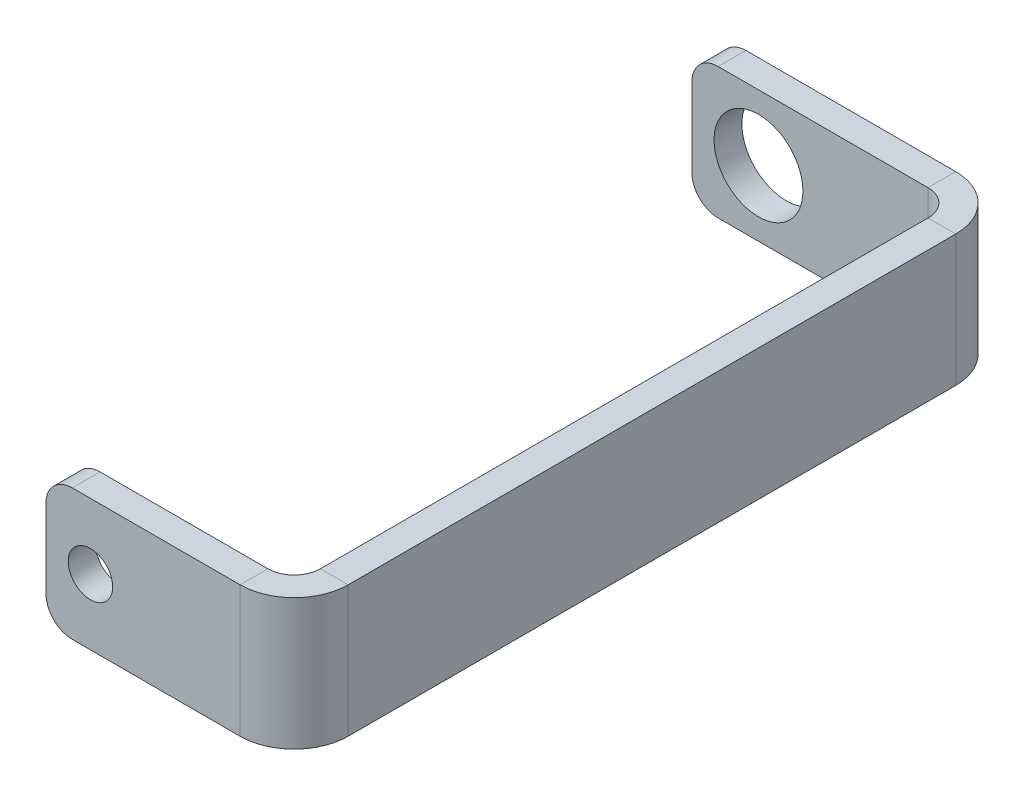
SolidWorks part; units mm, degrees
note: The reader was unsure of these and kept them because the rebuilt part matched: flange length of "Edge-Flange1", "Edge-Flange2".
material "Custom Plastic"
ref_plane "X-Y Datum" through (0, 0, 0) normal (0, 0, 1) x (1, 0, 0)
ref_plane "X-Z Datum" through (0, 0, 0) normal (0, 1, 0) x (1, 0, 0)
ref_plane "Y-Z Datum" through (0, 0, 0) normal (1, 0, 0) x (0, 0, -1)
sketch "Sketch1" plane through (0, 0, 0) normal (0, 0, 1) x (1, 0, 0)
  line L1 (-15, -7.5) -> (15, -7.5)
  line L2 (-15, -7.5) -> (-15, 7.5)
  line L3 (-15, 7.5) -> (15, 7.5)
  line L4 (15, -7.5) -> (15, 7.5)
  line L5 (-15, -7.5) -> (15, 7.5) construction
  line L6 (-15, 7.5) -> (15, -7.5) construction
  point P0 (0, 0)
  dimension "D1" = 30
  dimension "D2" = 15
base flange "Base-Flange1" sketch "Sketch1" thickness 3.175 reverse thickness direction no parameters "D1"=10
edge flange "Edge-Flange1" sketch "Sketch10" flange angle 90 flange length 78.652 flange position material outside bend radius 3 thickness 3.175 relief rectangular parameters "D6"=10
sketch "Sketch10" plane through (15, 0, 0) normal (-1, 0, 0) x (0, -1, 0)
  line L2 (-7.5, 0) -> (-7.5, 75.477)
  line L3 (-7.5, 75.477) -> (7.5, 75.477)
  line L4 (7.5, 75.477) -> (7.5, 0)
  line L5 (7.5, 0) -> (-7.5, 0) construction
  line L6 (7.5, 0) -> (-7.5, 0)
bend "EdgeBend1" bend radius 3 bend angle 90 parameters "D5"=1
edge flange "Edge-Flange2" sketch "Sketch13" flange angle 90 flange length 28.37 flange position material outside bend radius 3 thickness 3.175 relief rectangular parameters "D6"=10
sketch "Sketch13" plane through (15, 0, 75.477) normal (0, 0, -1) x (0, -1, 0)
  line L2 (-7.5, 0) -> (-7.5, 25.195)
  line L3 (-7.5, 25.195) -> (7.5, 25.195)
  line L4 (7.5, 25.195) -> (7.5, 0)
  line L5 (7.5, 0) -> (-7.5, 0) construction
  line L6 (7.5, 0) -> (-7.5, 0)
bend "EdgeBend2" bend radius 3 bend angle 90 parameters "D5"=2
sketch "Sketch14" plane through (0, 0, 0) normal (0, 0, 1) x (1, 0, 0)
  line L0 (-15, 0) -> (-7.38, 0)
  line L1 (-15, 7.5) -> (-15, -7.5) construction
  circle A0 centre (-7.38, 0) radius 5.08
  dimension "D1" = 10.16
  dimension "D2" = 7.62
extrude "Cut-Extrude1" cut sketch "Sketch14" against normal through all
sketch "Sketch15" plane through (0, 0, 78.652) normal (0, 0, 1) x (1, 0, 0)
  line L0 (-10.195, 0) -> (-5.115, 0)
  line L1 (-10.195, -7.5) -> (-10.195, 7.5) construction
  circle A0 centre (-5.115, 0) radius 2.54
  dimension "D1" = 5.08
extrude "Cut-Extrude2" cut sketch "Sketch15" against normal blind 10
fillet "Fillet1" radius 3 4 edges at (-10.195, 7.5, 77.0645) (-10.195, -7.5, 77.0645) (-15, 7.5, -1.5875) (-15, -7.5, -1.5875)
sketch "Bend-Lines1" [suppressed] plane through (0, 0, 0) normal (0, 1, 0) x (1, 0, 0)
sketch "Bounding-Box1" [suppressed] plane through (0, 0, 0) normal (0, 1, 0) x (1, 0, 0)
sheet metal parameters "Sheet-Metal1" thickness 3.175 parameters "D1"=10
flat pattern "Flat-Pattern1" [suppressed]
sketch "Bend-Lines2" plane through (0, 0, 0) normal (0, 1, 0) x (1, 0, 0)
sketch3d "Bounding-Box2" [suppressed]
  line L0 (-15, -7.5, 0) -> (15, -7.5, 0) construction
  line L1 (-15, 7.5, 0) -> (15, 7.5, 0) construction
  line L2 (-15, -7.5, 0) -> (-15, 7.5, 0) construction
  line L3 (15, -7.5, 0) -> (15, 7.5, 0) construction
sheet metal parameters "Sheet-Metal2" thickness 3.175 parameters "D1"=10
flat pattern "Flat-Pattern1"
sketch "Bend-Lines2" plane through (0, 0, 0) normal (0, 0, 1) x (1, 0, 0)
  line L0 (15.603, -7.5) -> (15.603, 7.5) construction
  line L1 (15.603, -7.5) -> (15.603, 7.5) construction
sketch3d "Bounding-Box2" [suppressed]
  line L0 (-15, -7.5, 0) -> (63.031, -7.5, 0) construction
  line L1 (-15, 7.5, 0) -> (63.031, 7.5, 0) construction
  line L2 (-15, -7.5, 0) -> (-15, 7.5, 0) construction
  line L3 (63.031, -7.5, 0) -> (63.031, 7.5, 0) construction
bend of the flat pattern "Flatten-<EdgeBend1>1"
sheet metal parameters "Sheet-Metal3" thickness 3.175 parameters "D1"=10
flat pattern "Flat-Pattern1" [suppressed]
sketch "Bend-Lines2" plane through (0, 0, 0) normal (0, 0, 1) x (1, 0, 0)
  line L0 (15.603, -7.5) -> (15.603, 7.5) construction
  line L1 (15.603, -7.5) -> (15.603, 7.5) construction
  line L2 (63.634, -7.5) -> (63.634, 7.5) construction
  line L3 (63.634, -7.5) -> (63.634, 7.5) construction
sketch3d "Bounding-Box2" [suppressed]
  line L0 (-15, -7.5, 0) -> (85.0621, -7.5, 0) construction
  line L1 (-15, 7.5, 0) -> (85.0621, 7.5, 0) construction
  line L2 (-15, -7.5, 0) -> (-15, 7.5, 0) construction
  line L3 (85.0621, -7.5, 0) -> (85.0621, 7.5, 0) construction
bend of the flat pattern "Flatten-<EdgeBend1>1"
bend of the flat pattern "Flatten-<EdgeBend2>1"
sheet metal parameters "Sheet-Metal4" thickness 3.175 parameters "D1"=10
flat pattern "Flat-Pattern1" [suppressed]
sketch "Bend-Lines2" plane through (0, 0, 0) normal (0, 0, 1) x (1, 0, 0)
  line L0 (13.103, -7.5) -> (13.103, 7.5) construction
  line L1 (13.103, -7.5) -> (13.103, 7.5) construction
  line L2 (88.086, -7.5) -> (88.086, 7.5) construction
  line L3 (88.086, -7.5) -> (88.086, 7.5) construction
sketch3d "Bounding-Box2" [suppressed]
  line L0 (-12.5, -7.5, 0) -> (115.5141, -7.5, 0) construction
  line L1 (-12.5, 7.5, 0) -> (115.5141, 7.5, 0) construction
  line L2 (-12.5, -7.5, 0) -> (-12.5, 7.5, 0) construction
  line L3 (115.5141, -7.5, 0) -> (115.5141, 7.5, 0) construction
bend of the flat pattern "Flatten-<EdgeBend1>1"
bend of the flat pattern "Flatten-<EdgeBend2>1"
sheet metal parameters "Sheet-Metal5" thickness 3.175 parameters "D1"=10
flat pattern "Flat-Pattern1"
sketch "Bend-Lines2" plane through (0, 0, 0) normal (0, 0, 1) x (1, 0, 0)
  line L0 (15.603, -7.5) -> (15.603, 7.5) construction
  line L1 (15.603, -7.5) -> (15.603, 7.5) construction
  line L2 (92.286, -7.5) -> (92.286, 7.5) construction
  line L3 (92.286, -7.5) -> (92.286, 7.5) construction
sketch3d "Bounding-Box2" [suppressed]
  line L0 (-15, -7.5, 0) -> (118.0841, -7.5, 0) construction
  line L1 (-15, 7.5, 0) -> (118.0841, 7.5, 0) construction
  line L2 (-15, -7.5, 0) -> (-15, 7.5, 0) construction
  line L3 (118.0841, -7.5, 0) -> (118.0841, 7.5, 0) construction
bend of the flat pattern "Flatten-<EdgeBend1>1"
bend of the flat pattern "Flatten-<EdgeBend2>1"
